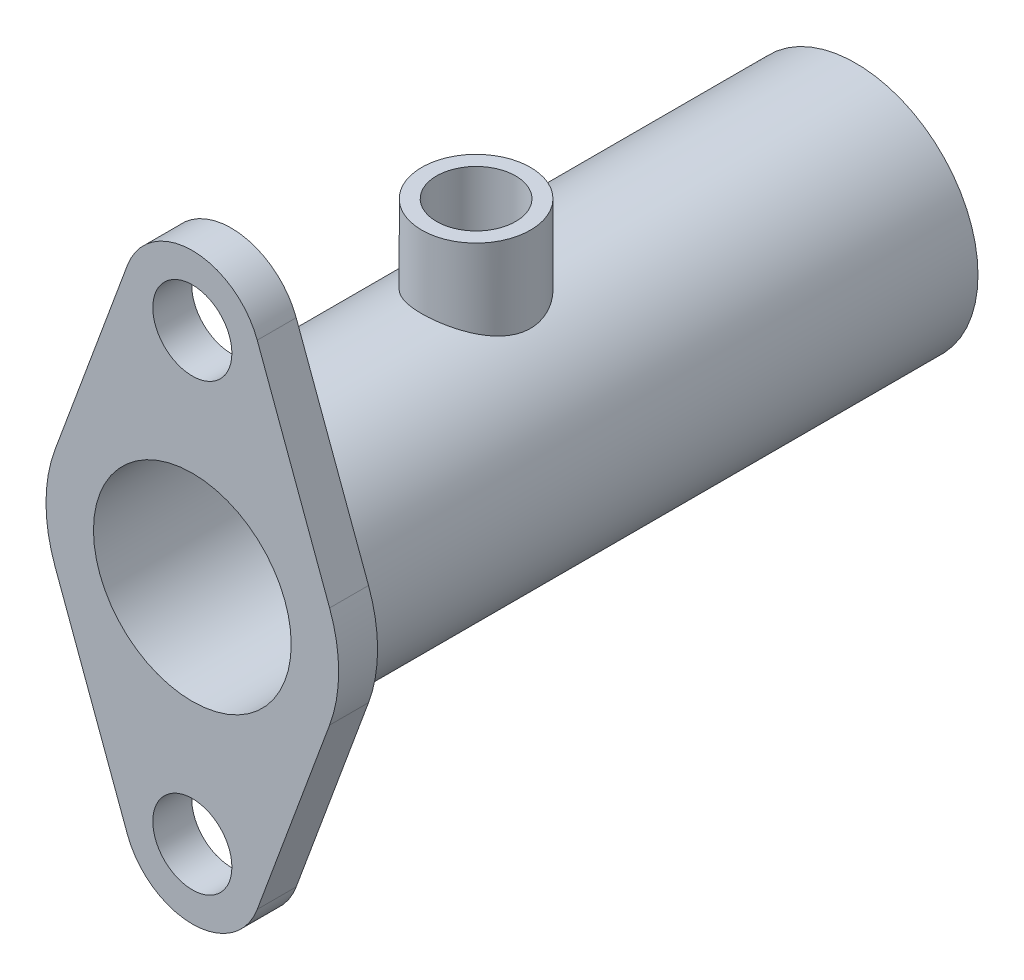
SolidWorks part; units mm, degrees
material "6061-T6 (SS)"
ref_plane "Front Plane" through (0, 0, 0) normal (0, 0, 1) x (1, 0, 0)
ref_plane "Top Plane" through (0, 0, 0) normal (0, 1, 0) x (1, 0, 0)
ref_plane "Right Plane" through (0, 0, 0) normal (1, 0, 0) x (0, 0, -1)
sketch "Sketch1" plane through (0, 0, 0) normal (0, 0, 1) x (1, 0, 0)
  line L0 (-17.6006, 0) -> (17.3059, 0) construction
  line L1 (-8.3387, 31.6569) -> (-17.6304, 6.5159)
  line L2 (8.3387, 31.6569) -> (17.6304, 6.5159)
  line L3 (-8.3387, -31.6569) -> (-17.6304, -6.5159)
  line L4 (8.3387, -31.6569) -> (17.6304, -6.5159)
  circle A0 centre (0, 0) radius 12.7
  circle A1 centre (0, 28.575) radius 8.89
  circle A2 centre (0, -28.575) radius 8.89
  circle A3 centre (0, 0) radius 18.796
  circle A4 centre (0, 28.575) radius 5.08
  circle A5 centre (0, -28.575) radius 5.08
  dimension "D1" = 25.4
  dimension "D3" = 17.78
  dimension "D4" = 37.592
  dimension "D5" = 10.16
  dimension "D2" = 57.15
extrude "Boss-Extrude1" add sketch "Sketch1" along normal blind 5 contours A1 A4 | A3 L2 A1 L1 | A3 A0 | A3 L3 A2 L4 | A2 A5 region at (0, 19.5813, 0) region at (0, 37.2136, 0) region at (0, 18.2644, 0) region at (0, -19.5813, 0) region at (-1.5211, -20.0714, 0)
sketch "Sketch2" plane through (0, 0, 0) normal (0, 0, -1) x (-1, 0, 0)
  circle A0 centre (0, 0) radius 15.7
  circle A1 centre (0, 0) radius 12.7
  dimension "D1" = 25.4
  dimension "D2" = 3
extrude "Boss-Extrude2" add sketch "Sketch2" along normal blind 77.216
sketch "Sketch3" plane through (0, 0, -77.216) normal (0, 0, -1) x (-1, 0, 0)
  circle A0 centre (0, 0) radius 15.7
  dimension "D1" = 31.4
extrude "Boss-Extrude3" add sketch "Sketch3" along normal blind 3
ref_plane "Plane1" through (0, 25, 0) normal (0, 1, 0) x (1, 0, 0)
sketch "Sketch4" plane through (0, 25, 0) normal (0, 1, 0) x (1, 0, 0)
  line L0 (15.7, 80.216) -> (-15.7, 80.216) construction
  circle A0 centre (0, 31.448) radius 6.985
  circle A1 centre (0, 31.448) radius 5.08
  dimension "D2" = 13.97
  dimension "D3" = 10.16
  dimension "D1" = 48.768
extrude "Boss-Extrude5" add sketch "Sketch4" against normal up to surface (9.3 mm away) contours A0 up to face at (15.7, 0, 0)
extrude "Cut-Extrude1" cut sketch "Sketch4<5>" against normal up to surface (12.3 mm away) contours A1 up to face at (12.7, 0, 5)
sketch "Sketch4<5>" plane through (0, 25, 0) normal (0, 1, 0) x (1, 0, 0) same geometry as "Sketch4"
